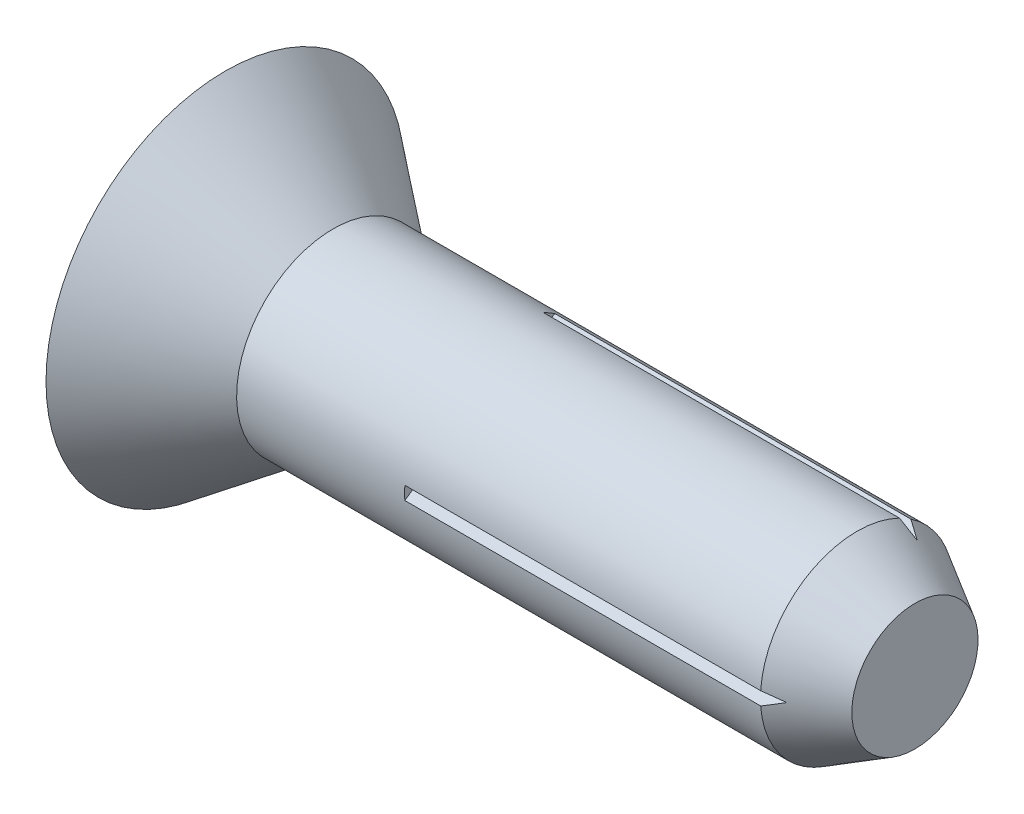
SolidWorks part; units mm, degrees
ref_plane "Front" through (0, 0, 0) normal (0, 0, 1) x (1, 0, 0)
ref_plane "Top" through (0, 0, 0) normal (0, 1, 0) x (1, 0, 0)
ref_plane "Right" through (0, 0, 0) normal (1, 0, 0) x (0, 0, -1)
sketch "Sketch1" plane through (2.3276, 1.6276, 0) normal (0, 0, 1) x (0, 1, 0)
  line L0 (-1.6276, -2.6724) -> (-1.1701, -2.6724)
  line L1 (-1.1701, -2.6724) -> (-0.9276, -2.2524)
  line L2 (-0.9276, -2.2524) -> (-0.9276, 2.3276)
  line L3 (-0.9276, 2.3276) -> (-1.6276, 2.3276)
  line L4 (-1.6276, 2.3276) -> (-1.6276, -2.6724)
  line L5 (-1.6276, 13.4318) -> (-1.6276, -14.8213) construction
  dimension "D3" = 30
revolve "Base-Revolve" add sketch "Sketch1" angle 360 about L5
ref_plane "Plane1" through (5, 0, 0) normal (1, 0, 0) x (0, 0, -1)
sketch "Sketch2" plane through (5, 0, 0) normal (1, 0, 0) x (0, 0, -1)
  line L0 (-0.049, -0.7) -> (0, -0.63)
  line L1 (0, -0.63) -> (0.049, -0.7)
  line L2 (0.049, -0.7) -> (-0.049, -0.7)
  line L3 (0, -1.1035) -> (0, 0.4817) construction
  dimension "D1" = 70
  dimension "D2" = 35
  dimension "D3" = 0.7
  dimension "D4" = 0.63
extrude "Cut-Extrude1" [suppressed] cut sketch "Sketch2" against normal blind 3.75
pattern_circular "CirPattern1" [suppressed] count 3 over 360 about axis through (-11.1041, 0, 0) along (1, 0, 0) of bodies 102
sketch "Sketch3" plane through (4.2526, 2.9526, 0) normal (0, 0, 1) x (0, 1, 0)
  line L0 (-2.9526, 4.2526) -> (-1.6526, 4.2526)
  line L1 (-3.4101, -0.7474) -> (-2.495, -0.7474) construction
  line L2 (-2.9526, 5.1526) -> (-2.9526, 4.2526)
  line L5 (-2.9526, 7.336) -> (-2.9526, -1.6257) construction
  arc A0 (-1.6526, 4.2526) -> (-2.9526, 5.1526) centre (-2.9526, 3.7637) ccw
  dimension "D1" = 5
  dimension "dk" = 2.6
revolve "Revolve1" [suppressed] add sketch "Sketch3" angle 360 about L5
sketch "Sketch6" plane through (5, 0, 0) normal (1, 0, 0) x (0, 0, -1)
  line L0 (-0.7, 0.049) -> (-0.63, 0)
  line L1 (-0.63, 0) -> (-0.7, -0.049)
  line L2 (-0.7, 0.049) -> (-0.7, -0.049)
  line L3 (-0.8611, 0) -> (0.1904, 0) construction
  dimension "D1" = 70
  dimension "D2" = 35
  dimension "D3" = 0.7
  dimension "D4" = 0.63
extrude "Cut-Extrude2" cut sketch "Sketch6" against normal blind 3
pattern_circular "CirPattern2" count 3 over 360 about axis through (-11.1041, 0, 0) along (1, 0, 0) of "Cut-Extrude2"
sketch "Sketch7" plane through (3.6006, 2.3006, 0) normal (0, 0, 1) x (0, 1, 0)
  line L0 (-2.3006, 4.0408) -> (-2.3006, -1.3994) construction
  line L2 (-2.3006, 3.6006) -> (-1.0006, 3.6006)
  line L3 (-1.0006, 3.6006) -> (-1.6006, 2.8186)
  line L4 (-1.6006, 2.8186) -> (-2.3006, 2.8186)
  line L5 (-2.3006, 3.6006) -> (-2.3006, 2.8186)
  dimension "D1" = 5
  dimension "dk" = 2.6
  dimension "D2" = 37.5
  dimension "D3" = 1.4
revolve "Revolve2" add sketch "Sketch7" angle 360 about L0
equation "\"D3@Sketch2\" = \"d@Sketch1\" / 2"
equation "\"D4@Sketch2\" = \"D3@Sketch2\" * 0.9"
equation "\"D1@Cut-Extrude1\" = \"l@Sketch1\" * 0.75"
equation "\"D3@Sketch6\" = \"d@Sketch1\" / 2"
equation "\"D4@Sketch6\" = \"D3@Sketch6\" * 0.9"
equation "\"D1@Cut-Extrude2\" = \"l@Sketch1\" * 0.6"
equation "\"D1@Sketch3\" = \"l@Sketch1\""
equation "\"D1@Sketch7\" = \"l@Sketch1\""
equation "\"D3@Sketch7\" = \"d@Sketch1\""
